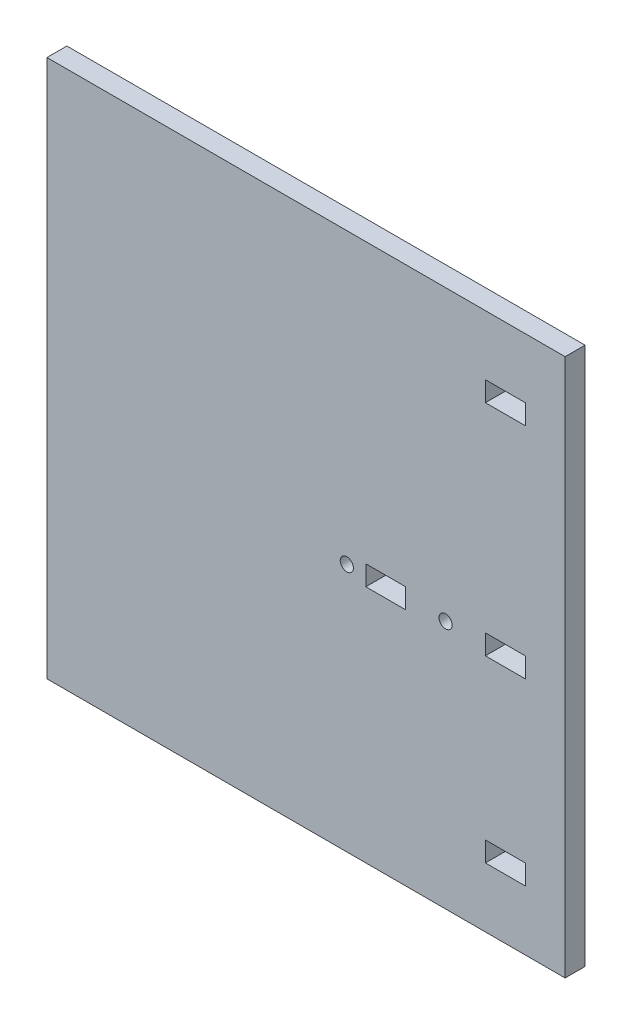
SolidWorks part; units mm, degrees
ref_plane "Front Plane" through (0, 0, 0) normal (0, 0, 1) x (1, 0, 0)
ref_plane "Top Plane" through (0, 0, 0) normal (0, 1, 0) x (1, 0, 0)
ref_plane "Right Plane" through (0, 0, 0) normal (1, 0, 0) x (0, 0, -1)
sketch "Sketch1" plane through (0, 0, 0) normal (0, 0, 1) x (1, 0, 0)
  line L1 (158.75, 155.575) -> (-6.35, 155.575)
  line L2 (158.75, 155.575) -> (158.75, -15.875)
  line L3 (158.75, -15.875) -> (-6.35, -15.875)
  line L4 (-6.35, 155.575) -> (-6.35, -15.875)
extrude "Boss-Extrude1" add sketch "Sketch1" along normal blind 6.35
sketch "Sketch2" plane through (0, 0, 6.35) normal (0, 0, 1) x (1, 0, 0)
  line L0 (122.7836, 66.675) -> (118.5164, 60.325) construction
  line L1 (146.05, 66.675) -> (133.35, 66.675)
  line L2 (146.05, 66.675) -> (146.05, 60.325)
  line L3 (146.05, 60.325) -> (133.35, 60.325)
  line L4 (133.35, 66.675) -> (133.35, 60.325)
  line L5 (107.95, 66.675) -> (95.25, 66.675)
  line L6 (107.95, 66.675) -> (107.95, 60.325)
  line L7 (107.95, 60.325) -> (95.25, 60.325)
  line L8 (95.25, 66.675) -> (95.25, 60.325)
  line L9 (122.7836, 60.325) -> (118.5164, 66.675) construction
  line L10 (91.3245, 60.325) -> (87.0573, 66.675) construction
  line L11 (91.3245, 66.675) -> (87.0573, 60.325) construction
  circle A0 centre (120.65, 63.5) radius 2.0955
  circle A1 centre (89.1909, 63.5) radius 2.0955
  dimension "D1" = 4.191
extrude "Cut-Extrude1" cut sketch "Sketch2" against normal through all
sketch "Sketch3" plane through (0, 0, 6.35) normal (0, 0, 1) x (1, 0, 0)
  line L0 (158.75, -15.875) -> (158.75, 155.575) construction
  line L1 (146.05, 9.525) -> (133.35, 9.525)
  line L2 (146.05, 9.525) -> (146.05, 3.175)
  line L3 (146.05, 3.175) -> (133.35, 3.175)
  line L4 (133.35, 9.525) -> (133.35, 3.175)
  line L5 (-6.35, -15.875) -> (158.75, -15.875) construction
  line L6 (158.75, 69.85) -> (109.7685, 69.85) construction
  line L7 (133.35, 130.175) -> (133.35, 136.525)
  line L8 (146.05, 136.525) -> (133.35, 136.525)
  line L9 (146.05, 130.175) -> (146.05, 136.525)
  line L10 (146.05, 130.175) -> (133.35, 130.175)
  dimension "D1" = 12.7
  dimension "D2" = 12.7
  dimension "D3" = 6.35
  dimension "D4" = 19.05
extrude "Cut-Extrude2" cut sketch "Sketch3" against normal through all
